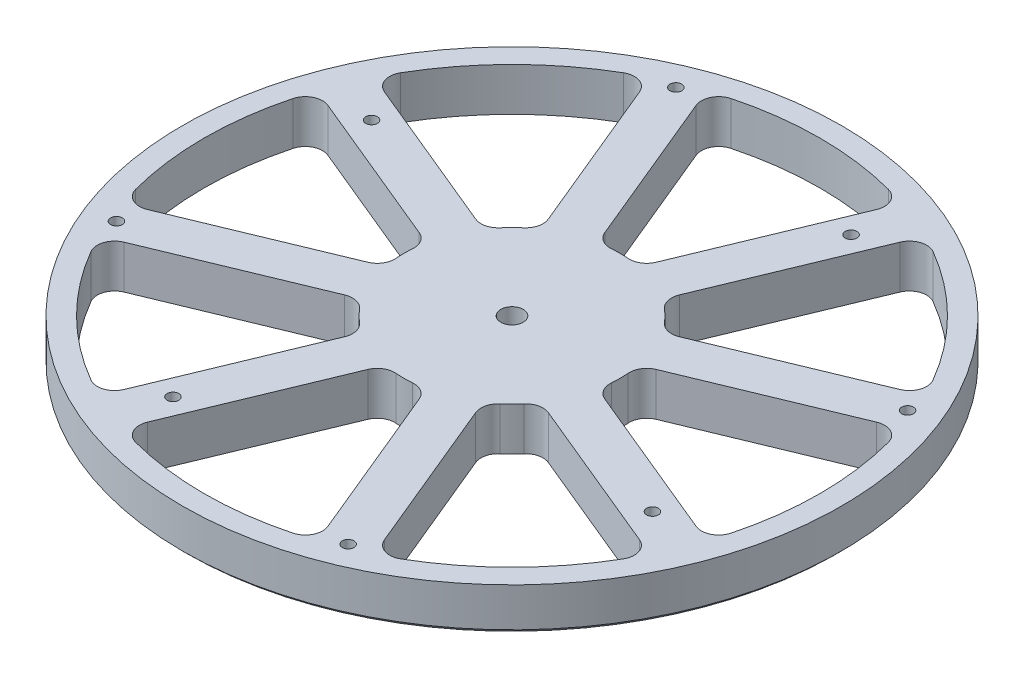
SolidWorks part; units mm, degrees
ref_plane "Front Plane" through (0, 0, 0) normal (0, 0, 1) x (1, 0, 0)
ref_plane "Top Plane" through (0, 0, 0) normal (0, 1, 0) x (1, 0, 0)
ref_plane "Right Plane" through (0, 0, 0) normal (1, 0, 0) x (0, 0, -1)
sketch "Sketch2" plane through (0, 0, 0) normal (1, 0, 0) x (0, 0, -1)
  line L0 (0, 0) -> (-76.2, 0)
  line L1 (-76.2, 0) -> (-76.2, 10)
  line L2 (-76.2, 10) -> (0, 10)
  line L5 (0, 10) -> (0, 0)
  dimension "D1" = 76.2
  dimension "D2" = 10
ref_axis "Axis1" through (0, -0.5, 0) along (0, 1, 0)
revolve "Revolve1" add sketch "Sketch2" angle 360 about axis through (0, -0.5, 0) along (0, 1, 0)
hole_wizard "#6-32 Tapped Hole1" positions "Sketch6" profile "Sketch7" tap size "#6-32" standard "ANSI Inch" end condition through all
sketch "Sketch6" plane through (0, 10, 0) normal (0, 1, 0) x (1, 0, 0)
  line L0 (0, 0) -> (-53.438, 129.0108) construction
  line L2 (0, 0) -> (0, 109.0908) construction
  line L3 (0, 0) -> (-70.3996, 29.1605) construction
  circle A0 centre (0, 0) radius 76.2 construction
  point P0 (-26.7878, 64.6716)
  point P18 (-55.4328, 22.961)
  dimension "D1" = 22.5
  dimension "D2" = 70
  dimension "D3" = 45
  dimension "D4" = 60
sketch "Sketch7" plane through (-26.7878, 10, -64.6716) normal (1, 0, 0) x (0, 0, 1)
  line L0 (0, 0) -> (0, 10)
  line L1 (0, 10) -> (1.3525, 10)
  line L2 (1.3525, 10) -> (1.3525, 0)
  line L5 (1.3525, 0) -> (0, 0)
  line L11 (0, -6.35) -> (0, 107.95) construction
  dimension "Thread Major Dia." = 2.7051
  dimension "Thru Tap Drill Depth" = 10
pattern_circular "CirPattern3" count 4 over 360 about axis through (0, -0.5, 0) along (0, 1, 0) of "#6-32 Tapped Hole1"
sketch "Sketch8" plane through (0, 10, 0) normal (0, 1, 0) x (1, 0, 0)
  line L4 (0, 0) -> (0, 93.9995) construction
  line L5 (0, 0) -> (113.8372, 0) construction
  line L6 (-4.7544, 24.5438) -> (-22.5604, 67.5312)
  line L7 (4.7544, 24.5438) -> (22.5604, 67.5312)
  line L8 (0, 0) -> (-26.7878, 64.6716) construction
  arc A0 (-4.7544, 24.5438) -> (4.7544, 24.5438) centre (0, 0) cw
  arc A1 (-22.5604, 67.5312) -> (22.5604, 67.5312) centre (0, 0) cw
  circle A2 centre (0, 0) radius 76.2 construction
  dimension "D1" = 25
  dimension "D2" = 5
  dimension "D3" = 5
extrude "Cut-Extrude1" cut sketch "Sketch8" against normal through all
fillet "Fillet1" radius 4 4 edges at (4.7544, 5, -24.5438) (22.5604, 5, -67.5312) (-4.7544, 5, -24.5438) (-22.5604, 5, -67.5312)
pattern_circular "CirPattern4" count 8 over 360 about axis through (0, -0.5, 0) along (0, 1, 0) of "Cut-Extrude1", "Fillet1"
chamfer "Chamfer2" distance 1 angle 45 1 edges at (0, 0, -76.2)
hole_wizard "#6 (0.204) Diameter Hole2" positions "Sketch9" profile "Sketch11" hole size "#6" standard "ANSI Inch" end condition through all
sketch "Sketch9" plane through (0, 0, 0) normal (0, -1, 0) x (-1, 0, 0)
  point P0 (0, 0)
sketch "Sketch11" plane through (0, 0, 0) normal (1, 0, 0) x (0, 0, -1)
  line L0 (0, 0) -> (0, 10)
  line L1 (0, 10) -> (2.5908, 10)
  line L2 (2.5908, 10) -> (2.5908, 0)
  line L5 (2.5908, 0) -> (0, 0)
  line L11 (0, -6.35) -> (0, 107.95) construction
  dimension "Thru Hole Dia." = 5.1816
  dimension "Thru Hole Depth" = 10
equation "\"TubeDiameter\" = 6.000in"
equation "\"D1@Sketch2\"=\"TubeDiameter\"/2"
